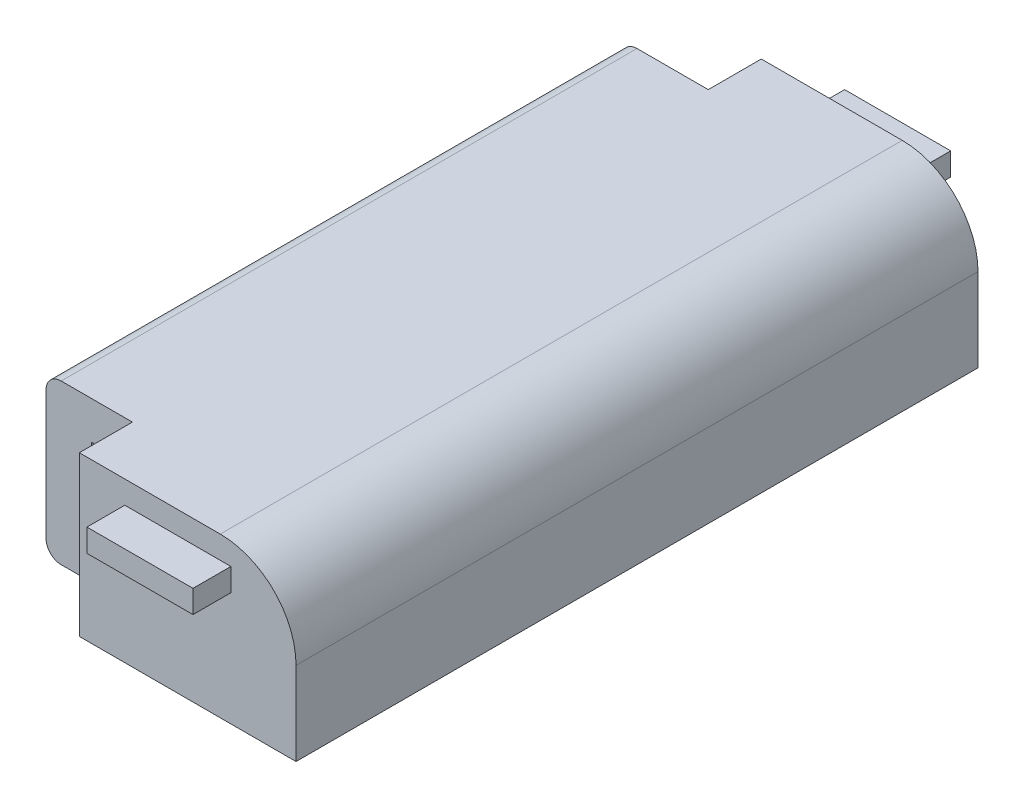
SolidWorks part; units mm, degrees
ref_plane "Front Plane" through (0, 0, 0) normal (0, 0, 1) x (1, 0, 0)
ref_plane "Top Plane" through (0, 0, 0) normal (0, 1, 0) x (1, 0, 0)
ref_plane "Right Plane" through (0, 0, 0) normal (1, 0, 0) x (0, 0, -1)
sketch "Sketch1" plane through (0, 0, 0) normal (0, 0, 1) x (1, 0, 0)
  line L0 (0, 0) -> (0, -20.32)
  line L1 (0, -20.32) -> (-7.62, -20.32)
  line L2 (-7.62, -20.32) -> (-7.62, 6.35)
  line L3 (-7.62, 6.35) -> (43.18, 6.35)
  line L4 (43.18, 6.35) -> (43.18, -20.32)
  line L7 (43.18, -20.32) -> (6.858, -20.32)
  line L8 (6.858, -20.32) -> (6.858, 0)
  line L9 (6.858, 0) -> (0, 0)
  point P7 (14.478, 7.9321)
  point P8 (0, 0)
  point P9 (-7.62, 6.9065)
  point P12 (49.0382, 6.9957)
  dimension "D1" = 6.858
  dimension "D2" = 7.62
  dimension "D3" = 20.32
  dimension "D4" = 6.35
  dimension "D5" = 50.8
extrude "Boss-Extrude1" add sketch "Sketch1" along normal blind 96.52
ref_plane "Plane2" through (0, 0, 48.26) normal (0, 0, -1) x (-1, 0, 0)
sketch "Sketch3" plane through (0, 0, 96.52) normal (0, 0, 1) x (1, 0, 0)
  line L1 (6.858, -20.32) -> (43.18, -20.32)
  line L2 (6.858, -20.32) -> (6.858, 6.35)
  line L3 (6.858, 6.35) -> (43.18, 6.35)
  line L4 (43.18, -20.32) -> (43.18, 6.35)
extrude "Boss-Extrude3" add sketch "Sketch3" along normal blind 8.89
sketch "Sketch2" plane through (0, 0, 105.41) normal (0, 0, -1) x (-1, 0, 0)
  line L0 (-43.18, 6.35) -> (7.62, 6.35) construction
  line L1 (-32.258, -1.27) -> (-14.478, -1.27)
  line L2 (-32.258, -1.27) -> (-32.258, 2.54)
  line L3 (-32.258, 2.54) -> (-14.478, 2.54)
  line L4 (-14.478, -1.27) -> (-14.478, 2.54)
  line L6 (-6.858, 0) -> (-6.858, -20.32) construction
  dimension "D1" = 3.81
  dimension "D2" = 17.78
  dimension "D3" = 3.81
  dimension "D4" = 7.62
extrude "Boss-Extrude4" add sketch "Sketch2" against normal blind 6.35
mirror "Mirror2" about plane through (0, 0, 48.26) normal (0, 0, -1) of "Boss-Extrude3", "Boss-Extrude4"
fillet "Fillet1" radius 12.7 1 edges at (43.18, 6.35, 48.26)
fillet "Fillet2" radius 2.54 2 edges at (-7.62, -20.32, 48.26) (-7.62, 6.35, 48.26)
